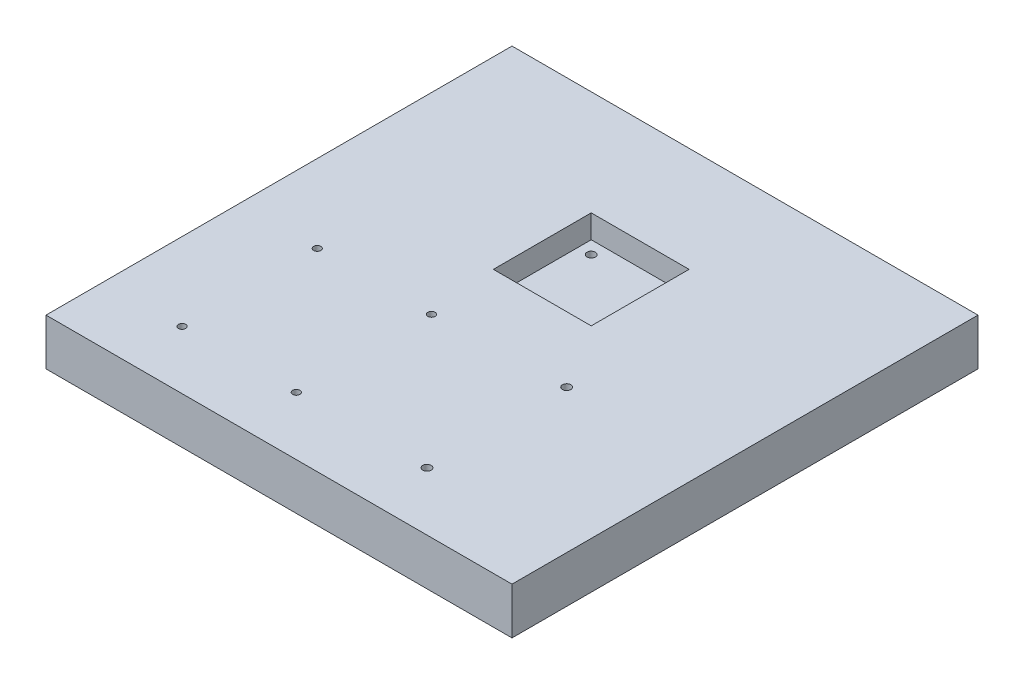
SolidWorks part; units mm, degrees
ref_plane "Front Plane" through (0, 0, 0) normal (0, 0, 1) x (1, 0, 0)
ref_plane "Top Plane" through (0, 0, 0) normal (0, 1, 0) x (1, 0, 0)
ref_plane "Right Plane" through (0, 0, 0) normal (1, 0, 0) x (0, 0, -1)
sketch "Sketch1" plane through (0, 0, 0) normal (0, 1, 0) x (1, 0, 0)
  line L1 (0, 0) -> (200, 0)
  line L2 (0, 0) -> (0, 200)
  line L3 (0, 200) -> (200, 200)
  line L4 (200, 0) -> (200, 200)
  dimension "D1" = 200
  dimension "D2" = 200
extrude "Base" add sketch "Sketch1" along normal blind 20
hole_wizard "Pi-MountHoles" positions "Sketch13" profile "Sketch14" counterbore size "M2.5" standard "ANSI Metric" end condition up to next
sketch "Sketch13" plane through (0, 0, 0) normal (0, -1, 0) x (-1, 0, 0)
  line L0 (0, 0) -> (-200, 0) construction
  point P0 (-33.42, 25)
  point P2 (-82.42, 25)
  point P4 (-82.42, 83)
  point P6 (-33.42, 83)
  point P17 (-100, 0)
  point P21 (0, 0)
  dimension "D1" = 49
  dimension "D2" = 58
  dimension "D3" = 25
  dimension "D4" = 17.58
sketch "Sketch14" plane through (33.42, 0, -25) normal (1, 0, 0) x (0, 0, -1)
  line L0 (0, 0) -> (0, 20)
  line L1 (0, 20) -> (1.55, 20)
  line L3 (1.55, 20) -> (1.55, 2.1)
  line L4 (3, 2.1) -> (1.55, 2.1)
  line L5 (3, 2.1) -> (3, 0.025)
  line L6 (3, 0.025) -> (3.025, 0)
  line L7 (3.025, 0) -> (0, 0)
  line L8 (-3, 0.025) -> (-3.025, 0) construction
  line L11 (0, -6.35) -> (0, 107.95) construction
  dimension "Thru Hole Dia." = 3.1
  dimension "Thru Hole Depth" = 20
  dimension "C'Bore Dia." = 6
  dimension "C'Bore Depth" = 2.1
  dimension "Near C'Sink Dia." = 6.05
  dimension "Near C'Sink Angle" = 90
hole_wizard "Battery-MountHoles" positions "Sketch15" profile "Sketch16" counterbore size "M3" standard "ANSI Metric" end condition up to next
sketch "Sketch15" plane through (0, 0, 0) normal (0, -1, 0) x (-1, 0, 0)
  line L0 (0, 0) -> (-200, 0) construction
  point P0 (-138.5, 25)
  point P2 (-138.5, 84.95)
  point P9 (-100, 0)
  dimension "D1" = 59.95
  dimension "D2" = 25
  dimension "D3" = 38.5
sketch "Sketch16" plane through (138.5, 0, -25) normal (1, 0, 0) x (0, 0, -1)
  line L0 (0, 0) -> (0, 20)
  line L1 (0, 20) -> (1.8, 20)
  line L3 (1.8, 20) -> (1.8, 2.4)
  line L4 (3.5, 2.4) -> (1.8, 2.4)
  line L5 (3.5, 2.4) -> (3.5, 0.025)
  line L6 (3.5, 0.025) -> (3.525, 0)
  line L7 (3.525, 0) -> (0, 0)
  line L8 (-3.5, 0.025) -> (-3.525, 0) construction
  line L11 (0, -6.35) -> (0, 107.95) construction
  dimension "Thru Hole Dia." = 3.6
  dimension "Thru Hole Depth" = 20
  dimension "C'Bore Dia." = 7
  dimension "C'Bore Depth" = 2.4
  dimension "Near C'Sink Dia." = 7.05
  dimension "Near C'Sink Angle" = 90
sketch "Sketch4" plane through (0, 20, 0) normal (0, 1, 0) x (1, 0, 0)
  line L0 (0, 0) -> (200, 0) construction
  line L1 (79, 155) -> (121, 155)
  line L2 (79, 155) -> (79, 113)
  line L3 (79, 113) -> (121, 113)
  line L4 (121, 155) -> (121, 113)
  circle A1 centre (82.42, 83) radius 1.55 construction
  point P8 (100, 0)
  point P9 (100, 113)
  dimension "D1" = 42
  dimension "D2" = 30
extrude "StepperSeat" cut sketch "Sketch4" against normal blind 10
hole_wizard "Stepper-MountHoles" positions "Sketch11" profile "Sketch12" counterbore size "M3" standard "ANSI Metric" end condition up to next
sketch "Sketch11" plane through (0, 0, 0) normal (0, -1, 0) x (-1, 0, 0)
  point P0 (-115.5, 149.5)
  point P2 (-84.5, 149.5)
  point P4 (-84.5, 118.5)
  point P6 (-115.5, 118.5)
  dimension "D1" = 31
  dimension "D2" = 31
  dimension "D3" = 5.5
  dimension "D4" = 5.5
sketch "Sketch12" plane through (115.5, 0, -149.5) normal (1, 0, 0) x (0, 0, -1)
  line L0 (0, 0) -> (0, 10)
  line L1 (0, 10) -> (1.8, 10)
  line L3 (1.8, 10) -> (1.8, 2.4)
  line L4 (3.5, 2.4) -> (1.8, 2.4)
  line L5 (3.5, 2.4) -> (3.5, 0.025)
  line L6 (3.5, 0.025) -> (3.525, 0)
  line L7 (3.525, 0) -> (0, 0)
  line L8 (-3.5, 0.025) -> (-3.525, 0) construction
  line L11 (0, -6.35) -> (0, 107.95) construction
  dimension "Thru Hole Dia." = 3.6
  dimension "Thru Hole Depth" = 10
  dimension "C'Bore Dia." = 7
  dimension "C'Bore Depth" = 2.4
  dimension "Near C'Sink Dia." = 7.05
  dimension "Near C'Sink Angle" = 90
